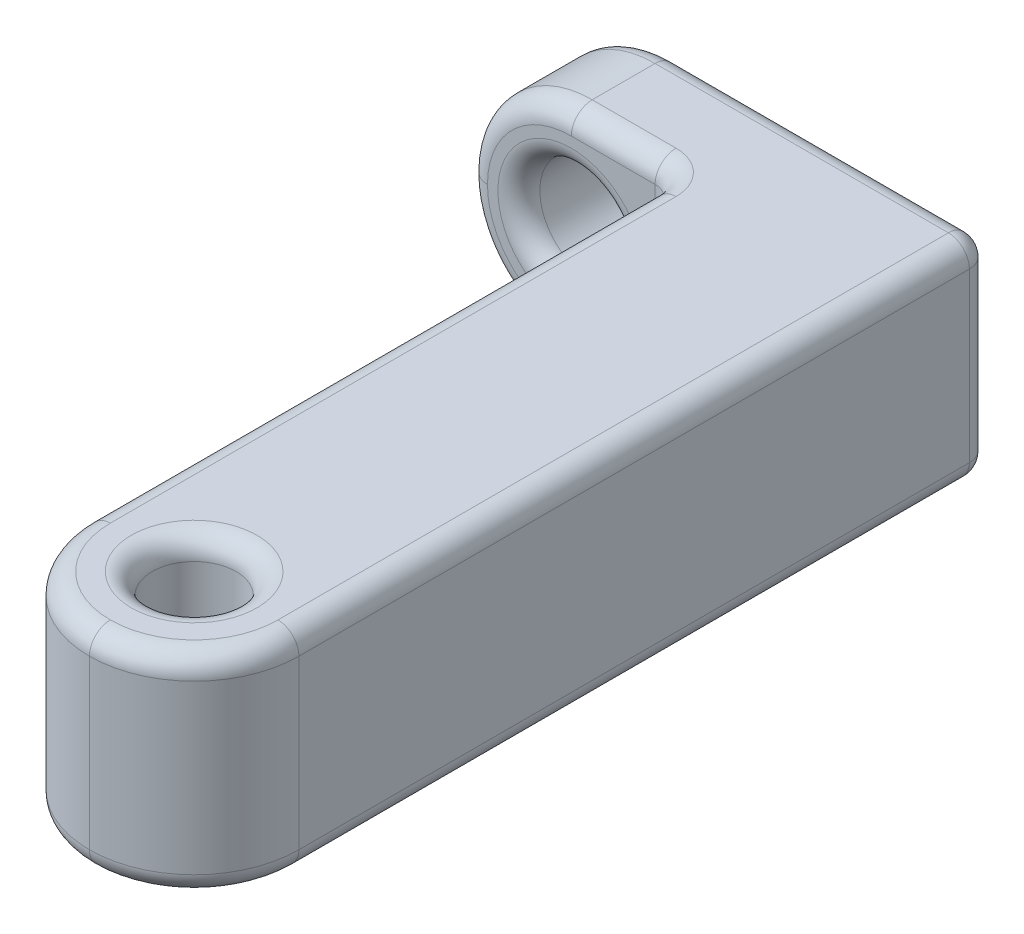
SolidWorks part; units mm, degrees
ref_plane "Front Plane" through (0, 0, 0) normal (0, 0, 1) x (1, 0, 0)
ref_plane "Top Plane" through (0, 0, 0) normal (0, 1, 0) x (1, 0, 0)
ref_plane "Right Plane" through (0, 0, 0) normal (1, 0, 0) x (0, 0, -1)
sketch "Sketch1" plane through (0, 0, 0) normal (0, 0, 1) x (1, 0, 0)
  line L0 (0, 5) -> (0, -5)
  line L1 (-10, -5) -> (10, -5)
  line L2 (-10, -5) -> (-10, 5)
  line L3 (-10, 5) -> (10, 5)
  line L4 (10, -5) -> (10, 5)
  line L5 (-10, -5) -> (10, 5) construction
  line L6 (-10, 5) -> (10, -5) construction
  circle A0 centre (-5, 0) radius 2.5
  point P0 (0, 0)
  dimension "D1" = 5
  dimension "D2" = 10
  dimension "D3" = 10
  dimension "D4" = 10
  dimension "D5" = 5
extrude "Boss-Extrude1" add sketch "Sketch1" along normal blind 5 contours L3 L2 L1 L0 A0 region at (-0.1414, 0, 0)
extrude "Boss-Extrude2" add sketch "Sketch1<4>" along normal blind 38 contours L1 L4 L3 L0 region at (5, 0, 0)
sketch "Sketch1<4>" plane through (0, 0, 0) normal (0, 0, 1) x (1, 0, 0) same geometry as "Sketch1"
sketch "Sketch2" plane through (0, -5, 0) normal (0, -1, 0) x (1, 0, 0)
  line L0 (0, 38) -> (0, 5) construction
  line L1 (-10, 0) -> (10, 0) construction
  line L2 (0, 36) -> (10, 36) construction
  line L3 (10, 38) -> (10, 0) construction
  line L4 (0, 38) -> (10, 38) construction
  circle A0 centre (5, 33) radius 2
  point P10 (0, 0)
  dimension "D1" = 4
  dimension "D2" = 5
  dimension "D3" = 33
  dimension "D4" = 36
  dimension "D5" = 5
extrude "Cut-Extrude1" cut sketch "Sketch2" against normal up to next
fillet "Fillet1" radius 5 4 edges at (-10, 5, 2.5) (-10, -5, 2.5) (10, 0, 38) (0, 0, 38)
fillet "Fillet2" radius 1 22 edges at (2.5, 5, 0) (10, 0, 0) (10, 5, 16.5) (5, 5, 35) (5, -5, 31) (0, -5, 19) (0, 5, 19) (10, -5, 16.5) (-2.5, 0, 0) (2.5, -5, 0) (-2.5, 0, 5) (-2.5, 5, 5) (-2.5, -5, 5) (0, 0, 5) (-8.5355, -3.5355, 0) (-8.5355, 3.5355, 0) (1.4645, 5, 36.5355) (8.5355, 5, 36.5355) (-8.5355, -3.5355, 5) (-8.5355, 3.5355, 5) (1.4645, -5, 36.5355) (8.5355, -5, 36.5355)
